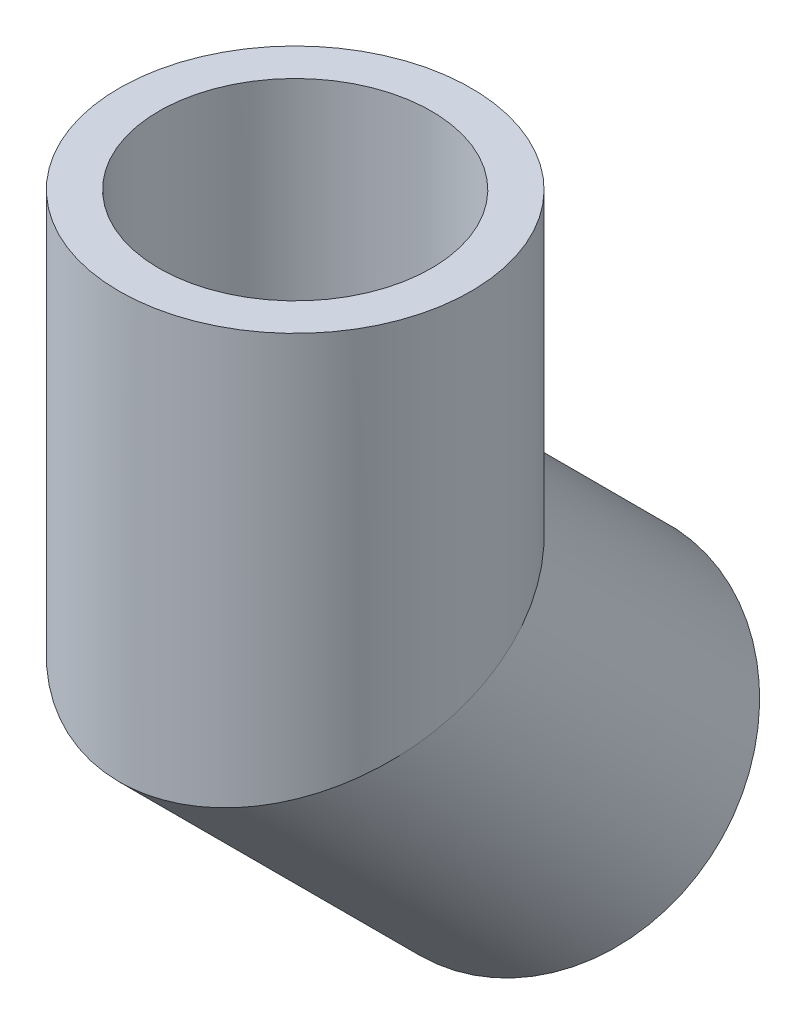
SolidWorks part; units mm, degrees
ref_plane "Front Plane" through (0, 0, 0) normal (0, 0, 1) x (1, 0, 0)
ref_plane "Top Plane" through (0, 0, 0) normal (0, 1, 0) x (1, 0, 0)
ref_plane "Right Plane" through (0, 0, 0) normal (1, 0, 0) x (0, 0, -1)
sketch "Sketch2" plane through (0, 0, 0) normal (0, 1, 0) x (1, 0, 0)
  circle A0 centre (0, 0) radius 12.7
  circle A1 centre (0, 0) radius 9.8298
  dimension "D1" = 25.4
  dimension "D2" = 2.8702
sketch "Sketch3" plane through (0, 0, 0) normal (1, 0, 0) x (0, 0, -1)
  line L0 (0, 0) -> (0, -25.4)
  line L1 (0, -25.4) -> (17.9605, -43.3605)
  dimension "D3" = 135
  dimension "D1" = 25.4
  dimension "D2" = 25.4
sweep "Sweep1" add profiles "Sketch2" path "Sketch3"
